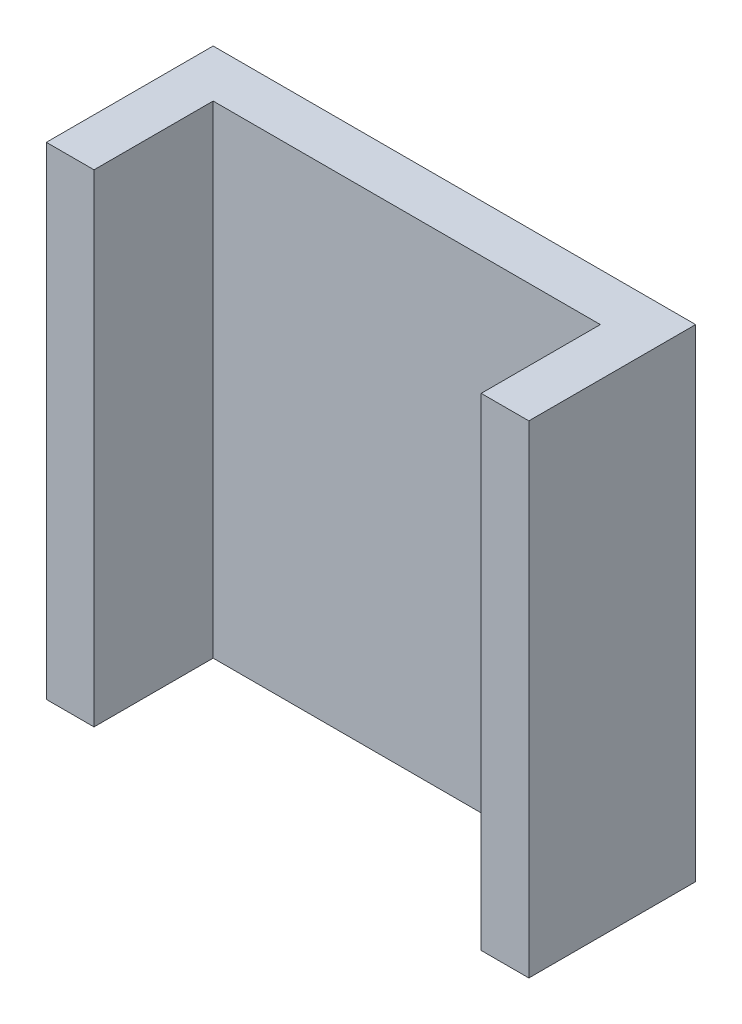
SolidWorks part; units mm, degrees
ref_plane "Plan de face" through (0, 0, 0) normal (0, 0, 1) x (1, 0, 0)
ref_plane "Plan de dessus" through (0, 0, 0) normal (0, 1, 0) x (1, 0, 0)
ref_plane "Plan de droite" through (0, 0, 0) normal (1, 0, 0) x (0, 0, -1)
sketch "Esquisse1" plane through (0, 0, 0) normal (0, 0, 1) x (1, 0, 0)
  line L1 (0, 0) -> (81, 0)
  line L2 (0, 0) -> (0, 81)
  line L3 (0, 81) -> (81, 81)
  line L4 (81, 0) -> (81, 81)
  dimension "D1" = 81
  dimension "D2" = 81
extrude "Boss.-Extru.1" add sketch "Esquisse1" along normal blind 8
sketch "Esquisse2" plane through (0, 0, 8) normal (0, 0, 1) x (1, 0, 0)
  line L4 (81, 81) -> (0, 81) construction
  line L6 (8, 81) -> (8, 0)
  line L8 (0, 81) -> (0, 0)
  line L9 (0, 0) -> (81, 0)
  line L10 (81, 0) -> (81, 81)
  line L11 (81, 81) -> (0, 81)
  line L12 (0, 81) -> (0, 0)
  line L13 (0, 0) -> (8, 0)
  line L14 (81, 0) -> (81, 81)
  line L15 (81, 81) -> (73, 81)
  line L16 (73, 81) -> (73, 0)
  line L17 (0, 0) -> (81, 0) construction
  line L18 (8, 81) -> (0, 81)
  line L19 (73, 0) -> (81, 0)
  point P6 (8, 73)
  point P11 (8, 8)
  point P12 (8, 0)
  point P15 (65, 0)
  point P16 (65, 73)
  dimension "D4" = 8
  dimension "D5" = 8
extrude "Boss.-Extru.2" add sketch "Esquisse2" along normal blind 20
equation "\"epaiss_cadre\"= 8"
equation "\"D2@Esquisse1\"=\"epaiss_cadre\"*2+65"
equation "\"D1@Esquisse1\"=\"epaiss_cadre\"*2+65"
equation "\"D1@Boss.-Extru.1\"=\"epaiss_cadre\""
equation "\"D4@Esquisse2\"=\"epaiss_cadre\""
equation "\"D5@Esquisse2\"=\"epaiss_cadre\""
